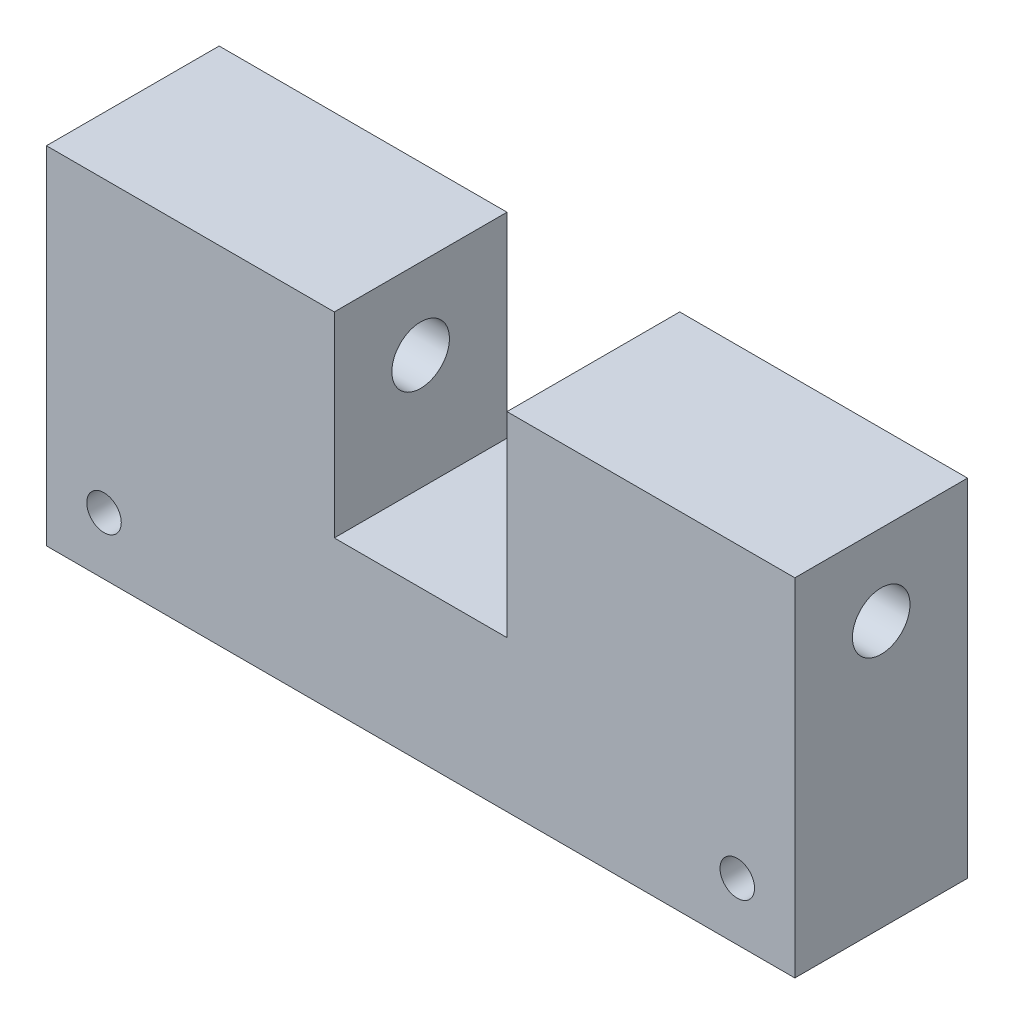
SolidWorks part; units mm, degrees
ref_plane "Front Plane" through (0, 0, 0) normal (0, 0, 1) x (1, 0, 0)
ref_plane "Top Plane" through (0, 0, 0) normal (0, 1, 0) x (1, 0, 0)
ref_plane "Right Plane" through (0, 0, 0) normal (1, 0, 0) x (0, 0, -1)
sketch "Sketch1" plane through (0, 0, 0) normal (0, 0, 1) x (1, 0, 0)
  line L0 (42.5, -5) -> (42.5, -14.5) construction
  line L1 (-22.5, -14.5) -> (42.5, -14.5)
  line L2 (-22.5, -14.5) -> (-22.5, 15.6)
  line L3 (-22.5, 15.6) -> (42.5, 15.6)
  line L4 (42.5, -14.5) -> (42.5, 15.6)
  line L5 (34.5, 2.6) -> (27.7, 2.6) construction
  circle A0 centre (-17.5, -9.5) radius 1.5
  circle A1 centre (37.5, -9.5) radius 1.5
  dimension "D1" = 0
  dimension "D2" = 13
extrude "Boss-Extrude1" add sketch "Sketch1" along normal blind 15
sketch "Sketch2" plane through (-22.5, 0, 0) normal (-1, 0, 0) x (0, 0, 1)
  line L0 (15, 15.6) -> (15, -14.5) construction
  line L1 (15, 15.6) -> (0, 15.6) construction
  circle A0 centre (7.5, 8.6) radius 2.5
  dimension "D1" = 5
  dimension "D2" = 7.5
  dimension "D3" = 7
extrude "Cut-Extrude1" cut sketch "Sketch2" against normal blind 75
sketch "Sketch3" plane through (0, 0, 15) normal (0, 0, 1) x (1, 0, 0)
  line L0 (42.5, 15.6) -> (-22.5, 15.6) construction
  line L1 (2.5, 15.6) -> (17.5, 15.6)
  line L2 (2.5, 15.6) -> (2.5, -1.4)
  line L3 (2.5, -1.4) -> (17.5, -1.4)
  line L4 (17.5, 15.6) -> (17.5, -1.4)
  line L5 (10, 15.6) -> (10, -27.8113) construction
  dimension "D1" = 17
  dimension "D2" = 15
  dimension "D3" = 7.5
extrude "Cut-Extrude2" cut sketch "Sketch3" against normal blind 75
